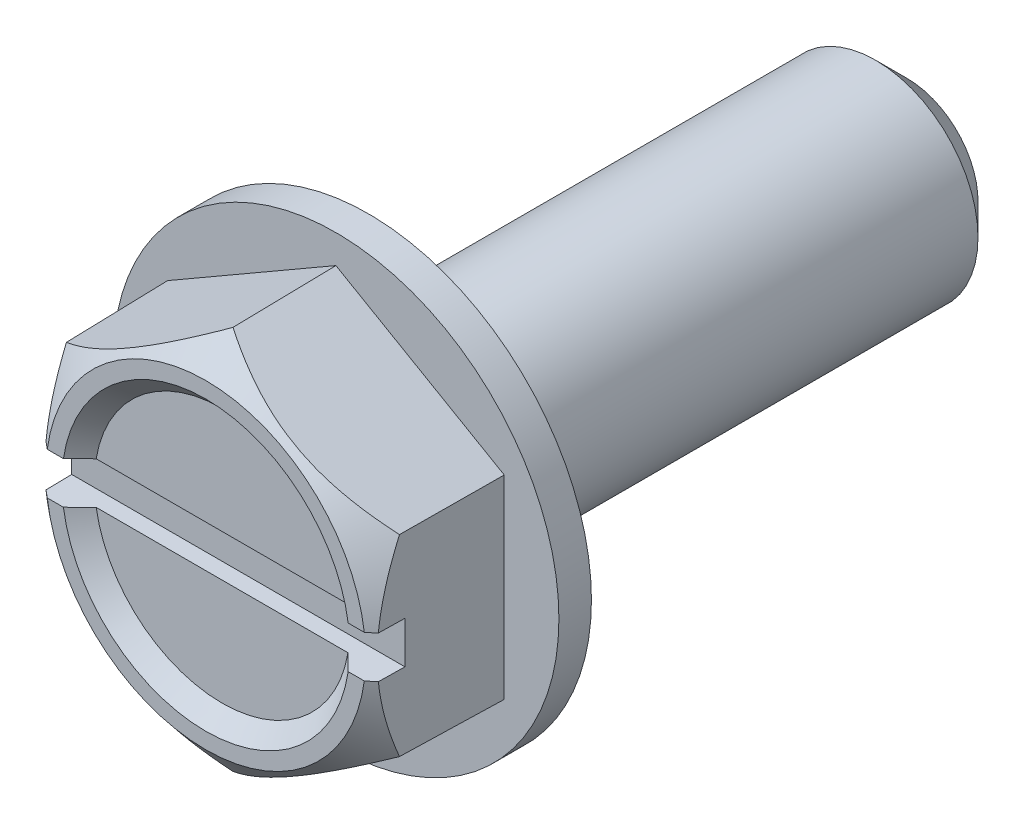
SolidWorks part; units mm, degrees
material "Chrome Stainless Steel"
ref_plane "Front Plane" through (0, 0, 0) normal (0, 0, 1) x (1, 0, 0)
ref_plane "Top Plane" through (0, 0, 0) normal (0, 1, 0) x (1, 0, 0)
ref_plane "Right Plane" through (0, 0, 0) normal (1, 0, 0) x (0, 0, -1)
sketch "Sketch1" plane through (0, 0, 0) normal (1, 0, 0) x (0, 0, -1)
  line L0 (0, 0) -> (12.7, 0) construction
  line L1 (12.7, 2.413) -> (12.7, -2.413) construction
  line L2 (0, 5.2578) -> (0, -5.2578) construction
  line L3 (3.8354, 0) -> (-3.8354, 0) construction
  line L4 (-3.8354, 3.9687) -> (-3.8354, -3.9688) construction
  line L5 (12.6339, 2.5276) -> (13.6922, 2.5276) construction
  line L6 (13.6922, 2.5276) -> (13.163, 1.611) construction
  line L7 (13.163, 1.611) -> (12.6339, 2.5276) construction
  line L8 (12.6669, 2.4703) -> (13.6591, 2.4703) construction
  line L9 (12.7, 2.413) -> (13.626, 2.413) construction
  line L10 (13.0969, 1.7256) -> (13.2292, 1.7256) construction
  line L11 (13.163, 2.413) -> (13.163, 2.5276) construction
  line L12 (13.163, 1.7256) -> (13.163, 1.611) construction
  point P6 (12.7, 0)
  point P8 (0, 0)
  point P11 (0, 0)
  point P15 (-3.8354, 0)
  point P20 (8.9958, -2.413)
  point P27 (13.163, 2.4703)
  dimension "Screw Size Decimal Equivalent" = 4.826
  dimension "Length" = 12.7
  dimension "Flange Diameter" = 10.5156
  dimension "Head Width" = 7.9375
  dimension "Head Height" = 3.8354
  dimension "D1" = 60
  dimension "Pitch" = 1.0583
  dimension "D2" = 0.1323
  dimension "D3" = 3.7042
sketch "Sketch2" plane through (0, 0, 0) normal (1, 0, 0) x (0, 0, -1)
  line L0 (0, 0) -> (0, 2.413)
  line L1 (0, 5.2578) -> (0, -5.2578) construction
  line L2 (0, 2.413) -> (11.9592, 2.413)
  line L3 (11.9592, 2.413) -> (12.7, 1.6722)
  line L4 (12.7, 2.413) -> (12.7, -2.413) construction
  line L5 (12.7, 1.6722) -> (12.7, 0)
  line L6 (12.7, 0) -> (0, 0)
  dimension "D1" = 45
  dimension "D2" = 0.7408
revolve "Revolve1" add sketch "Sketch2" angle 360 about L6
sketch "Sketch3" plane through (0, 0, 0) normal (0, 0, 1) x (1, 0, 0)
  line L0 (0, 5.2578) -> (0, -5.2578) construction
  circle A0 centre (0, 0) radius 5.2578
extrude "Boss-Extrude1" add sketch "Sketch3" along normal blind 0.7671
sketch "Sketch4" plane through (0, 0, 0.7671) normal (0, 0, 1) x (1, 0, 0)
  line L0 (0, 3.9687) -> (0, -3.9688) construction
  line L1 (-3.9687, 2.2914) -> (-3.9687, -2.2914)
  line L2 (-3.9687, -2.2914) -> (0, -4.5827)
  line L3 (0, -4.5827) -> (3.9688, -2.2914)
  line L4 (3.9688, -2.2914) -> (3.9687, 2.2914)
  line L5 (3.9687, 2.2914) -> (0, 4.5827)
  line L6 (0, 4.5827) -> (-3.9687, 2.2914)
  circle A0 centre (0, 0) radius 3.9687 construction
extrude "Boss-Extrude2" add sketch "Sketch4" along normal up to vertex (3.0683 mm away) draft 1 up to point (0, 0, 3.8354)
sketch "Sketch5" plane through (0, 0, 3.8354) normal (0, 0, 1) x (1, 0, 0)
  circle A0 centre (0, 0) radius 3.7703
  dimension "D1" = 7.5406
extrude "Cut-Extrude1" cut sketch "Sketch5" against normal through all draft 50 flip side to cut
sketch "Sketch6" plane through (0, 0, 3.8354) normal (0, 0, 1) x (1, 0, 0)
  circle A0 centre (0, 0) radius 3.3933
  dimension "D1" = 6.7866
extrude "Cut-Extrude2" cut sketch "Sketch6" against normal blind 0.3835 draft 45
sketch "Sketch10" plane through (0, 0, 0) normal (0, 0, 1) x (1, 0, 0)
  line L1 (-4.1672, 0.4961) -> (4.1672, 0.4961)
  line L2 (-4.1672, 0.4961) -> (-4.1672, -0.4961)
  line L3 (-4.1672, -0.4961) -> (4.1672, -0.4961)
  line L4 (4.1672, 0.4961) -> (4.1672, -0.4961)
  line L5 (0, -0.4961) -> (0, 0.4961) construction
  line L6 (-4.1672, 0) -> (4.1672, 0) construction
  point P108 (0, 0)
  dimension "D1" = 0.9922
  dimension "D2" = 8.3344
extrude "Cut-Extrude3" cut sketch "Sketch10" against normal blind 0.7671 from vertex starting at point (0, 0, 3.8354)
split "Split1" [suppressed] bodies to split 114
sketch "Sketch7" [suppressed] plane through (0, 0, 0) normal (1, 0, 0) x (0, 0, -1)
  line L0 (12.6669, 2.4703) -> (13.6591, 2.4703)
  line L1 (13.6591, 2.4703) -> (13.2292, 1.7256)
  line L2 (13.2292, 1.7256) -> (13.0969, 1.7256)
  line L3 (13.0969, 1.7256) -> (12.6669, 2.4703)
sketch "Sketch8" [suppressed] plane through (0, 0, -12.7) normal (0, 0, -1) x (-1, 0, 0)
  circle A0 centre (0, 0) radius 2.413
curve "Helix/Spiral1" [suppressed] pitch 1.0583 height 13.7583 turns 13
sweep "Cut-Sweep1" [suppressed] cut profiles "Sketch7" path "Helix/Spiral1"
combine bodies "Combine1" [suppressed] operation type add bodies to combine 110 111
sketch "Sketch9" [suppressed] plane through (0, 0, 0) normal (0, 0, -1) x (-1, 0, 0)
  circle A0 centre (0, 0) radius 2.413
extrude "Boss-Extrude3" [suppressed] add sketch "Sketch9" along normal through all draft 20
equation "\"D2@Sketch1\"=\"Pitch@Sketch1\"/8"
equation "\"D3@Sketch1\"=\"Pitch@Sketch1\"*3.5"
equation "\"D2@Sketch2\"=\"Pitch@Sketch1\"*.7"
equation "\"D1@Boss-Extrude1\"=\"Head Height@Sketch1\"*.2"
equation "\"D1@Sketch5\"=\"Head Width@Sketch1\"*.95"
equation "\"D1@Sketch6\"=\"D1@Sketch5\"*.9"
equation "\"D1@Cut-Extrude2\"=\"Head Height@Sketch1\"*.1"
equation "\"D4@Helix/Spiral1\"=\"Pitch@Sketch1\""
equation "\"D3@Helix/Spiral1\"=\"Length@Sketch1\"+\"Pitch@Sketch1\""
equation "\"D1@Sketch10\"=\"Head Width@Sketch1\"/8"
equation "\"D2@Sketch10\"=\"Head Width@Sketch1\"*1.05"
equation "\"D1@Cut-Extrude3\"=\"Head Height@Sketch1\"/5"
